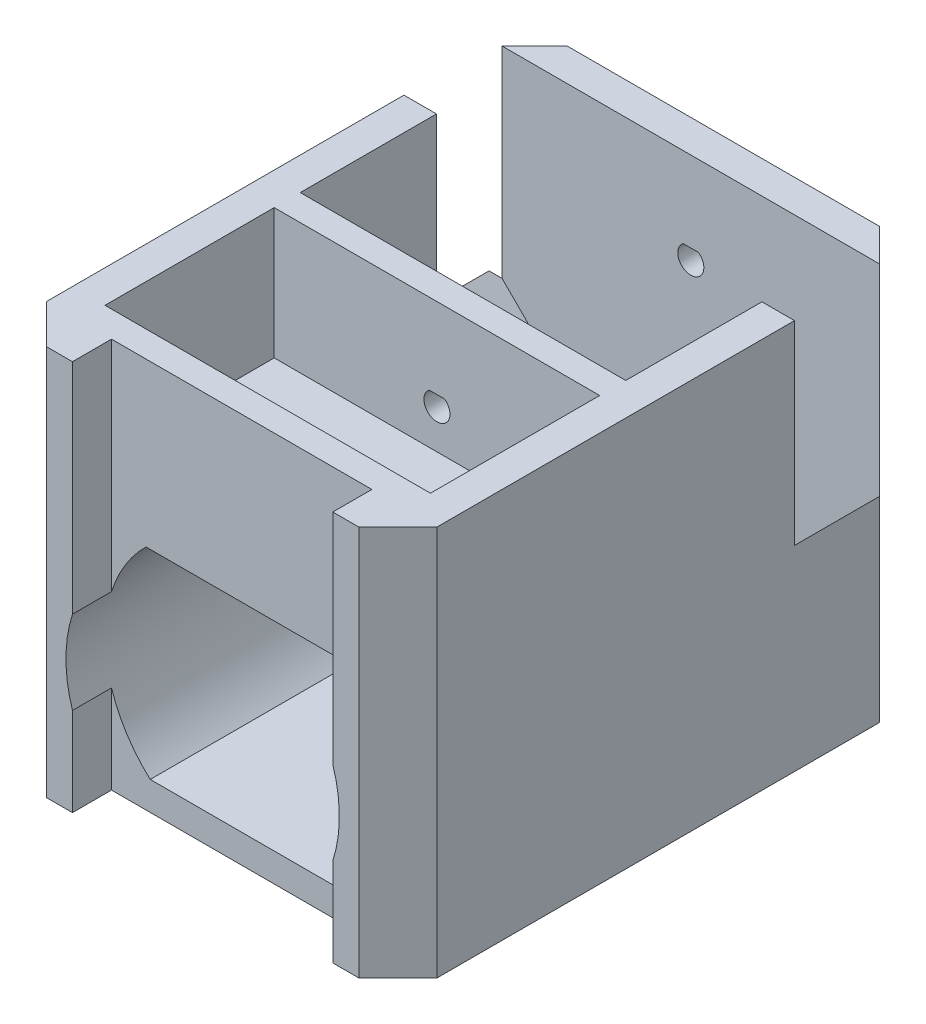
SolidWorks part; units mm, degrees
ref_plane "Front Plane" through (0, 0, 0) normal (0, 0, 1) x (1, 0, 0)
ref_plane "Top Plane" through (0, 0, 0) normal (0, 1, 0) x (1, 0, 0)
ref_plane "Right Plane" through (0, 0, 0) normal (1, 0, 0) x (0, 0, -1)
sketch "Sketch1" plane through (0, 0, 0) normal (0, 0, 1) x (1, 0, 0)
  line L1 (-15, -20) -> (15, -20)
  line L2 (-15, -20) -> (-15, 20)
  line L3 (-15, 20) -> (15, 20)
  line L4 (15, -20) -> (15, 20)
  line L5 (-15, -20) -> (15, 20) construction
  line L6 (-15, 20) -> (15, -20) construction
  point P0 (0, 0)
  dimension "D1" = 30
  dimension "D2" = 40
extrude "Boss-Extrude1" add sketch "Sketch1" along normal blind 40
sketch "Sketch2" plane through (0, 0, 40) normal (0, 0, 1) x (1, 0, 0)
  line L5 (-7.3485, -2.5) -> (7.3485, -2.5)
  line L7 (-7.0259, -17.803) -> (7.0259, -17.803)
  arc A2 (7.0259, -17.803) -> (7.3485, -2.5) centre (0, -10) ccw
  arc A3 (-7.3485, -2.5) -> (-7.0259, -17.803) centre (0, -10) ccw
  point P0 (0, -10)
  dimension "D1" = 21
extrude "Cut-Extrude1" cut sketch "Sketch2" against normal blind 35
sketch "Sketch4" plane through (0, 20, 0) normal (0, 1, 0) x (1, 0, 0)
  line L1 (-12.5, -37.5) -> (12.5, -37.5)
  line L2 (-12.5, -37.5) -> (-12.5, -2.5)
  line L3 (-12.5, -2.5) -> (12.5, -2.5)
  line L4 (12.5, -37.5) -> (12.5, -2.5)
  point P0 (0, -20)
  dimension "D1" = 25
  dimension "D2" = 35
extrude "Cut-Extrude3" cut sketch "Sketch4" against normal blind 20
sketch "Sketch5" plane through (0, 0, 0) normal (0, 1, 0) x (1, 0, 0)
  line L0 (12.5, -37.5) -> (12.5, -2.5) construction
  line L1 (-12.5, -2.5) -> (12.5, -2.5)
  line L2 (-12.5, -2.5) -> (-12.5, -20)
  line L3 (-12.5, -20) -> (12.5, -20)
  line L4 (12.5, -2.5) -> (12.5, -20)
extrude "Cut-Extrude4" cut sketch "Sketch5" against normal blind 20
sketch "Sketch13" plane through (0, 0, 0) normal (0, 1, 0) x (1, 0, 0)
  line L0 (12.5, -37.5) -> (12.5, -20) construction
  line L1 (-12.5, -20) -> (12.5, -20)
  line L2 (-12.5, -20) -> (-12.5, -22.0007)
  line L3 (-12.5, -22.0007) -> (12.5, -22.0007)
  line L4 (12.5, -20) -> (12.5, -22.0007)
extrude "Boss-Extrude3" add sketch "Sketch13" along normal up to surface (20 mm away) up to face at (0, 20, 20)
sketch "Sketch8" plane through (0, 0, 40) normal (0, 0, 1) x (1, 0, 0)
  line L0 (-0.5467, -9.1627) -> (0.5467, -9.1627)
  arc A0 (-0.5467, -9.1627) -> (0.5467, -9.1627) centre (0, -10) ccw
  dimension "D1" = 2
extrude "Cut-Extrude5" cut sketch "Sketch8" against normal up to surface (40 mm away) up to face at (0, 0, 0)
sketch "Sketch9" plane through (0, 0, 0) normal (0, 0, -1) x (-1, 0, 0)
  line L1 (-0.5842, 3.8116) -> (0.5842, 3.8116)
  arc A0 (-0.5842, 3.8116) -> (0.5842, 3.8116) centre (0, 3) ccw
  dimension "D2" = 2
extrude "Cut-Extrude6" cut sketch "Sketch9" against normal up to surface (40 mm away) up to face at (0, -10.1864, 40)
sketch "Sketch10" plane through (0, 0, 40) normal (0, 0, 1) x (1, 0, 0)
  line L0 (15, -20) -> (15, 20) construction
  line L1 (-15, 20) -> (15, 20)
  line L2 (-15, 20) -> (-15, 10)
  line L3 (-15, 10) -> (15, 10)
  line L4 (15, 20) -> (15, 10)
  dimension "D1" = 10
extrude "Cut-Extrude9" cut sketch "Sketch10" against normal up to surface (40 mm away) up to face at (0, 2.9058, 0)
chamfer "Chamfer2" distance 3 angle 45 4 edges at (15, -5, 0) (15, -5, 40) (-15, -5, 40) (-15, -5, 0)
sketch "Sketch16" plane through (-12.5, 0, 0) normal (1, 0, 0) x (0, 0, -1)
  line L1 (-2.5, 10) -> (-9.5368, 10)
  line L2 (-2.5, 10) -> (-2.5, -4.4568)
  line L4 (-9.5368, 10) -> (-9.5368, -4.4568)
  line L5 (-9.5368, -4.4568) -> (-2.5, -4.4568)
extrude "Cut-Extrude10" cut sketch "Sketch16" against normal mid plane 57
chamfer "Chamfer3" distance 3 angle 45 2 edges at (12.5, -4.4568, 6.0184) (-12.5, -4.4568, 6.0184)
sketch "Sketch17" plane through (0, 10, 0) normal (0, 1, 0) x (1, 0, 0)
  line L0 (12.5, -37.5) -> (12.5, -22.0007) construction
  line L1 (-12.5, -37.5) -> (12.5, -37.5)
  line L2 (-12.5, -37.5) -> (-12.5, -35)
  line L3 (-12.5, -35) -> (12.5, -35)
  line L4 (12.5, -37.5) -> (12.5, -35)
  dimension "D1" = 2.5
extrude "Boss-Extrude4" add sketch "Sketch17" against normal up to surface (10 mm away) up to face at (0, 0, 29.7504)
sketch "Sketch18" plane through (0, 10, 0) normal (0, 1, 0) x (1, 0, 0)
  line L0 (-10, -40) -> (10, -40)
  line L1 (-12, -40) -> (12, -40) construction
  line L5 (-10, -40) -> (10, -40)
  line L6 (-10, -40) -> (-10, -37)
  line L7 (-10, -37) -> (10, -37)
  line L8 (10, -40) -> (10, -37)
  point P5 (0, -40)
  line M15 (-12, -40) -> (12, -40)
  dimension "D1" = 20
  dimension "D2" = 3
extrude "Cut-Extrude13" cut sketch "Sketch18" against normal up to surface (30 mm away) contours L8 L7 L6 M15 region at (0, 10, 38.5) up to face at (0, -20, 11.25)
